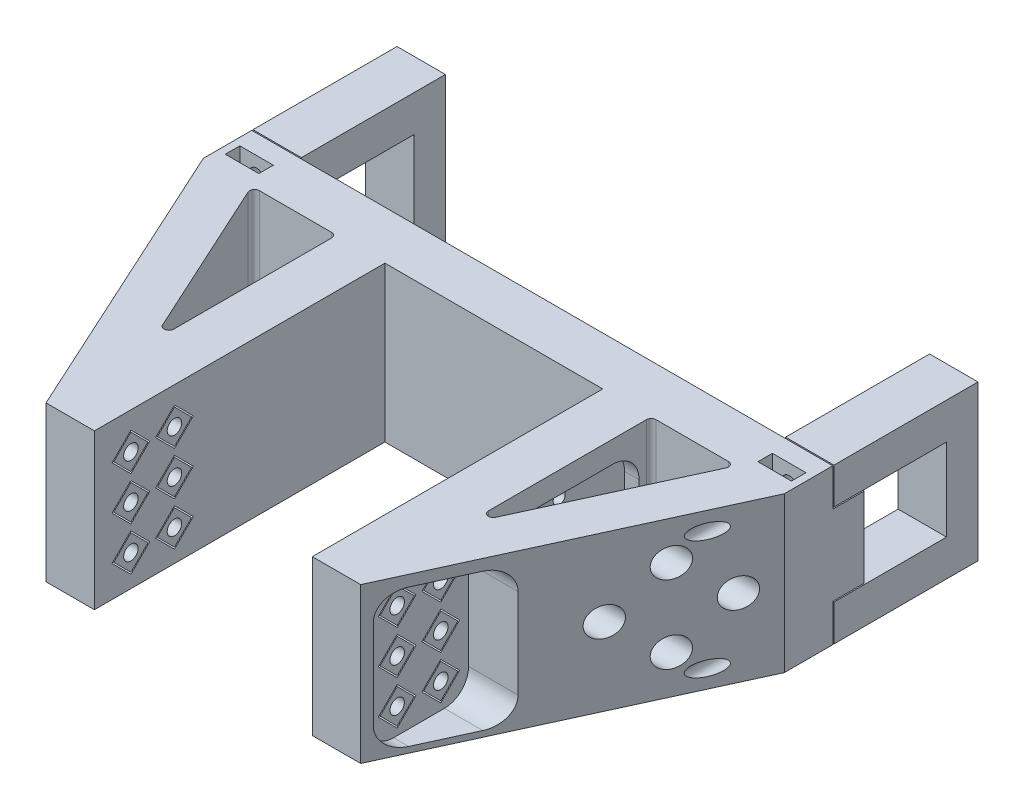
SolidWorks part; units mm, degrees
ref_plane "Front Plane" through (0, 0, 0) normal (0, 0, 1) x (1, 0, 0)
ref_plane "Top Plane" through (0, 0, 0) normal (0, 1, 0) x (1, 0, 0)
ref_plane "Right Plane" through (0, 0, 0) normal (1, 0, 0) x (0, 0, -1)
ref_axis "X" through (-88.99, 0, 0) along (1, 0, 0)
ref_axis "Y" through (0, 55, 0) along (0, -1, 0)
ref_axis "Z" through (0, 0, -88.99) along (0, 0, 1)
sketch "Sketch1" plane through (0, 0, 0) normal (0, 1, 0) x (1, 0, 0)
  line L0 (-50, 0) -> (50, 0)
  line L1 (50, 0) -> (50, 30)
  line L2 (50, 30) -> (60, 30)
  line L3 (60, 30) -> (60, -10)
  line L4 (60, -10) -> (32.5, -10)
  line L5 (32.5, -10) -> (32.5, -70)
  line L6 (32.5, -70) -> (22.5, -70)
  line L7 (22.5, -70) -> (22.5, -10)
  line L8 (22.5, -10) -> (-22.5, -10)
  line L9 (0, 0) -> (0, -10) construction
  line L10 (60, -10) -> (32.5, -70)
  line L11 (32.5, -48.1818) -> (50, -10)
  line L12 (-32.5, -48.1818) -> (-50, -10)
  line L13 (-60, -10) -> (-32.5, -70)
  line L14 (-22.5, -70) -> (-22.5, -10)
  line L15 (-32.5, -70) -> (-22.5, -70)
  line L16 (-32.5, -10) -> (-32.5, -70)
  line L17 (-60, -10) -> (-32.5, -10)
  line L18 (-60, 30) -> (-60, -10)
  line L19 (-50, 30) -> (-60, 30)
  line L20 (-50, 0) -> (-50, 30)
  dimension "D1" = 50
  dimension "D2" = 60
  dimension "D3" = 10
  dimension "D4" = 10
  dimension "D5" = 10
  dimension "D6" = 30
  dimension "D7" = 120
  dimension "D8" = 100
  dimension "D9" = 45
extrude "Main Extrude" add sketch "Sketch1" along normal mid plane 32 contours L0 L9 L8 L7 L6 L5 L4 L3 L2 L1 | L9 L0 L20 L19 L18 L17 L16 L15 L14 L8 | L11 L5 L10 L4 | L17 L13 L16 L12 region at (-25, 0, 1.1662) region at (25, 0, 1.1662) region at (-43.9352, 0, 34.9495) region at (43.9352, 0, 34.9495)
sketch "Sketch2" plane through (0, 0, 0) normal (1, 0, 0) x (0, 0, -1)
  line L0 (0, 0) -> (15, 0) construction
  line L1 (6.5, 8.5) -> (23.5, 8.5)
  line L2 (6.5, 8.5) -> (6.5, -8.5)
  line L3 (6.5, -8.5) -> (23.5, -8.5)
  line L4 (23.5, 8.5) -> (23.5, -8.5)
  line L5 (6.5, 8.5) -> (23.5, -8.5) construction
  line L6 (6.5, -8.5) -> (23.5, 8.5) construction
  point P0 (15, 0)
  dimension "D1" = 17
  dimension "D2" = 15
extrude "Drive Motor Cutout" cut sketch "Sketch2" against normal through all both and the other way through all
fillet "Sharp Edge Removal" radius 1 6 edges at (32.5, 0, 48.1818) (50, 0, 10) (32.5, 0, 10) (-32.5, 0, 48.1818) (-50, 0, 10) (-32.5, 0, 10)
sketch3d "Component Placement"
  line L0 (0, 0, 0) -> (0, 0, 10) construction
  line L1 (0, 0, 10) -> (0, 0, 26) construction
  line L2 (0, 0, 26) -> (22.5, 0, 26) construction
  dimension "D1" = 16
sketch "Weapon Motor Mount Holes" plane through (32.5, 0, 0) normal (1, 0, 0) x (0, 0, -1)
  line L0 (-34, -11.5) -> (-18, -11.5)
  line L1 (-12.5, -6) -> (-12.5, 6)
  line L2 (-18, 11.5) -> (-34, 11.5)
  line L3 (-39.5, 6) -> (-39.5, -6)
  line L4 (-39, 6) -> (-39, -6)
  line L5 (-34, -11) -> (-18, -11)
  line L6 (-13, -6) -> (-13, 6)
  line L7 (-18, 11) -> (-34, 11)
  line L8 (-39, 6) -> (-39, -6) construction
  line L9 (-34, -11) -> (-18, -11) construction
  line L10 (-13, -6) -> (-13, 6) construction
  line L11 (-18, 11) -> (-34, 11) construction
  circle A0 centre (-16.5, 0) radius 1.25 construction
  circle A1 centre (-35.5, 0) radius 1.25 construction
  circle A2 centre (-26, 8) radius 1.25 construction
  circle A3 centre (-26, -8) radius 1.25 construction
  circle A4 centre (-16.5, 0) radius 1.25
  circle A5 centre (-35.5, 0) radius 1.25
  circle A6 centre (-26, 8) radius 1.25
  circle A7 centre (-26, -8) radius 1.25
  circle A8 centre (-26, 8) radius 3
  circle A9 centre (-16.5, 0) radius 3
  circle A10 centre (-26, -8) radius 3
  circle A11 centre (-35.5, 0) radius 3
  arc A12 (-39.5, -6) -> (-34, -11.5) centre (-34, -6) ccw
  arc A13 (-18, -11.5) -> (-12.5, -6) centre (-18, -6) ccw
  arc A14 (-12.5, 6) -> (-18, 11.5) centre (-18, 6) ccw
  arc A15 (-34, 11.5) -> (-39.5, 6) centre (-34, 6) ccw
  arc A16 (-39, -6) -> (-34, -11) centre (-34, -6) ccw
  arc A17 (-18, -11) -> (-13, -6) centre (-18, -6) ccw
  arc A18 (-13, 6) -> (-18, 11) centre (-18, 6) ccw
  arc A19 (-34, 11) -> (-39, 6) centre (-34, 6) ccw
  arc A20 (-39, -6) -> (-34, -11) centre (-34, -6) ccw construction
  arc A21 (-18, -11) -> (-13, -6) centre (-18, -6) ccw construction
  arc A22 (-13, 6) -> (-18, 11) centre (-18, 6) ccw construction
  arc A23 (-34, 11) -> (-39, 6) centre (-34, 6) ccw construction
  dimension "D1" = 6
  dimension "D2" = 0
  dimension "D3" = 0.5
extrude "Cut-Extrude1" cut sketch "Weapon Motor Mount Holes" against normal up to surface (10 mm away) contours A5 | A6 | A4 | A7 region at (32.5, 0, 16.5) region at (32.5, 0, 35.5) region at (32.5, 8, 26) region at (32.5, -8, 26) up to face at (22.5, 0, 40)
extrude "Cut-Extrude2" cut sketch "Weapon Motor Mount Holes<3>" along normal through all contours A9 | A8 | A11 | A10
sketch "Weapon Motor Mount Holes<3>" plane through (32.5, 0, 0) normal (1, 0, 0) x (0, 0, -1) same geometry as "Weapon Motor Mount Holes"
extrude "Cut-Extrude3" cut sketch "Weapon Motor Mount Holes<4>" against normal blind 3 contours A15 L3 A12 L0 A13 L1 A14 L2
sketch "Weapon Motor Mount Holes<4>" plane through (32.5, 0, 0) normal (1, 0, 0) x (0, 0, -1) same geometry as "Weapon Motor Mount Holes"
sketch "Sketch4" plane through (0, 0, 0) normal (1, 0, 0) x (0, 0, -1)
  line L0 (0, 16) -> (0, -16) construction
  line L1 (0, 16) -> (0, -16)
  line L2 (6.5, -8.5) -> (6.5, 8.5) construction
  line L3 (6.5, -8.5) -> (6.5, 8.5)
  line L4 (6.5, 8.5) -> (0, 8.5)
  line L5 (6.5, -8.5) -> (0, -8.5)
  line L6 (6.5, -8.5) -> (6.5, -8.25)
  line L7 (6.5, -8.25) -> (0.25, -8.25)
  line L8 (6.5, 8.5) -> (6.5, 8.25)
  line L9 (6.5, 8.25) -> (0.25, 8.25)
  line L10 (0, 16) -> (0.25, 16)
  line L11 (0.25, 16) -> (0.25, 8.25)
  line L12 (0, -16) -> (0.25, -16)
  line L13 (0.25, -16) -> (0.25, -8.25)
  line L14 (0.25, 8.25) -> (0, 8.25)
  line L16 (0.25, -8.25) -> (0, -8.25)
  dimension "D1" = 0.25
extrude "Cut-Extrude4" cut sketch "Sketch4" against normal through all both and the other way through all contours L11 L10 L1 L4 L8 L9 | L14 L11 L4 L1 | L4 L11 L9 L3 | L12 L13 L5 L1 | L13 L16 L1 L5 | L13 L5 L3 L7 region at (0, 12.25, -0.125) region at (0, 8.375, -0.125) region at (0, 8.375, -3.375) region at (0, -8.375, -0.125) region at (0, -12.25, -0.125) region at (0, -8.375, -3.375)
sketch "Sketch5" plane through (0, 0, -0.25) normal (0, 0, 1) x (1, 0, 0)
  line L0 (55, 16) -> (55, 8.5) construction
  line L1 (55, -8.5) -> (55, -16) construction
  line L4 (50, 8.5) -> (60, 8.5)
  line L5 (60, 8.5) -> (60, 16)
  line L6 (60, 16) -> (50, 16)
  line L7 (50, 16) -> (50, 8.5)
  line L8 (50, 8.5) -> (60, 8.5)
  line L9 (60, 8.5) -> (60, 16)
  line L10 (60, 16) -> (50, 16)
  line L11 (50, 16) -> (50, 8.5)
  line L12 (50, -8.5) -> (50, -16)
  line L13 (50, -16) -> (60, -16)
  line L14 (60, -16) -> (60, -8.5)
  line L15 (60, -8.5) -> (50, -8.5)
  line L16 (50, -8.5) -> (50, -16)
  line L17 (50, -16) -> (60, -16)
  line L18 (60, -16) -> (60, -8.5)
  line L19 (60, -8.5) -> (50, -8.5)
  circle A0 centre (55, 12.25) radius 1.5
  circle A1 centre (55, -12.25) radius 1.5
  circle A2 centre (55, 12.25) radius 3
  circle A3 centre (55, -12.25) radius 3
  dimension "D3" = 3
  dimension "D4" = 6
  dimension "D1" = 0
  dimension "D2" = 0
extrude "Cut-Extrude5" cut sketch "Sketch5" against normal through all and the other way through all contours A0 | A1 region at (55, 12.25, -0.25) region at (55, -12.25, -0.25)
extrude "Cut-Extrude6" cut sketch "Sketch5<3>" along normal blind 4 from surface contours A2 | A3 starting at face at (56.5, 12.25, -30)
sketch "Sketch5<3>" plane through (0, 0, -0.25) normal (0, 0, 1) x (1, 0, 0) same geometry as "Sketch5"
ref_plane "Plane1" through (0, 0, 4) normal (0, 0, -1) x (-1, 0, 0)
sketch "Sketch6" plane through (0, 0, 4) normal (0, 0, -1) x (-1, 0, 0)
  line L0 (60, 16) -> (-60, 16) construction
  line L1 (-58.4641, 12.25) -> (-56.7321, 9.25)
  line L2 (-56.7321, 9.25) -> (-53.2679, 9.25)
  line L3 (-53.2679, 9.25) -> (-51.5359, 12.25)
  line L4 (-51.5359, 12.25) -> (-53.2679, 15.25) construction
  line L5 (-53.2679, 15.25) -> (-56.7321, 15.25) construction
  line L6 (-56.7321, 15.25) -> (-58.4641, 12.25) construction
  line L7 (-53.2679, -15.25) -> (-51.5359, -12.25) construction
  line L8 (-51.5359, -12.25) -> (-53.2679, -9.25)
  line L9 (-53.2679, -9.25) -> (-56.7321, -9.25)
  line L10 (-56.7321, -9.25) -> (-58.4641, -12.25)
  line L11 (-58.4641, -12.25) -> (-56.7321, -15.25) construction
  line L12 (-56.7321, -15.25) -> (-53.2679, -15.25) construction
  line L13 (60, 16) -> (-60, 16)
  line L14 (60, -16) -> (-60, -16) construction
  line L15 (60, -16) -> (-60, -16)
  line L16 (-58.4641, 12.25) -> (-58.4641, 16)
  line L17 (-51.5359, 12.25) -> (-51.5359, 16)
  line L18 (-58.4641, -12.25) -> (-58.4641, -16)
  line L19 (-51.5359, -12.25) -> (-51.5359, -16)
  circle A0 centre (-55, -12.25) radius 1.5 construction
  circle A1 centre (-55, 12.25) radius 1.5 construction
  circle A2 centre (-55, -12.25) radius 1.5 construction
  circle A3 centre (-55, 12.25) radius 1.5 construction
  circle A4 centre (-55, 12.25) radius 3 construction
  circle A5 centre (-55, -12.25) radius 3 construction
  dimension "D1" = 6
extrude "Cut-Extrude7" cut sketch "Sketch6" against normal blind 3 contours L3 L17 L13 L16 L1 L2 | L19 L8 L9 L10 L18 L15 region at (55, 12.9219, 4) region at (55, -12.9219, 4)
mirror "Mirror1" about plane through (0, 0, 0) normal (1, 0, 0) of "Cut-Extrude7", "Cut-Extrude6", "Cut-Extrude5"
sketch "Sketch7" plane through (0, 0, 0) normal (1, 0, 0) x (0, 0, -1)
  line L0 (-62.4645, 12) -> (-58.9289, 8.4645)
  line L1 (-62.4645, 12) -> (-66, 8.4645)
  line L2 (-58.9289, 8.4645) -> (-62.4645, 4.9289)
  line L3 (-66, 8.4645) -> (-62.4645, 4.9289)
  line L4 (-62.4645, 12) -> (-62.4645, 4.9289) construction
  line L5 (-58.9289, 8.4645) -> (-66, 8.4645) construction
  line L6 (-62.4645, 16) -> (-62.4645, 12) construction
  line L7 (-66, 8.4645) -> (-70, 8.4645) construction
  line L8 (-70, 16) -> (-70, -16) construction
  line L9 (-70, 16) -> (-10, 16) construction
  line L30 (-62.4645, 12.3536) -> (-58.5754, 8.4645)
  line L31 (-58.5754, 8.4645) -> (-62.4645, 4.5754)
  line L32 (-66.3536, 8.4645) -> (-62.4645, 4.5754)
  line L33 (-62.4645, 12.3536) -> (-66.3536, 8.4645)
  circle A0 centre (-62.4645, 8.4645) radius 1.5
  point P1 (-62.4645, 8.4645)
  dimension "D7" = 3
  dimension "D1" = 5
  dimension "D2" = 4
  dimension "D3" = 0.25
extrude "Cut-Extrude8" cut sketch "Sketch7" against normal through all both and the other way through all contours L30 L33 L32 L31 L3 L1 L0 L2 | A0 region at (0, 10.3312, 60.5977) region at (0, 8.4645, 62.4645)
pattern_linear "LPattern1" count 3 spacing 9 along (0, -1, 0) count 2 spacing 9 along (0, 0, -1) of "Cut-Extrude8"
sketch "Sketch8" plane through (0, 0, 0) normal (1, 0, 0) x (0, 0, -1)
  line L0 (-58.9289, -0.5355) -> (-57, -0.5355) construction
  line L1 (-68.2145, -14.7855) -> (-47.7145, -14.7855)
  line L2 (-68.2145, -14.7855) -> (-68.2145, 13.7145)
  line L3 (-68.2145, 13.7145) -> (-47.7145, 13.7145)
  line L4 (-47.7145, -14.7855) -> (-47.7145, 13.7145)
  line L5 (-68.2145, -14.7855) -> (-47.7145, 13.7145) construction
  line L6 (-68.2145, 13.7145) -> (-47.7145, -14.7855) construction
  point P0 (-57.9645, -0.5355)
  point P9 (-57.9645, -0.5355)
  dimension "D1" = 28.5
  dimension "D2" = 20.5
extrude "Cut-Extrude13" cut sketch "Sketch8" against normal through all from surface starting at face at (-32.5, 0, 27.3)
extrude "Cut-Extrude14" cut sketch "Sketch8<2>" along normal through all from surface starting at face at (32.5, 0, 26)
sketch "Sketch8<2>" plane through (0, 0, 0) normal (1, 0, 0) x (0, 0, -1) same geometry as "Sketch8"
fillet "Fillet1" radius 5 8 edges at (-32.9092, -14.7855, 68.2145) (-32.9092, 13.7145, 68.2145) (-37.6071, 13.7145, 47.7145) (-37.6071, -14.7855, 47.7145) (32.9092, 13.7145, 68.2145) (32.9092, -14.7855, 68.2145) (37.6071, -14.7855, 47.7145) (37.6071, 13.7145, 47.7145)
